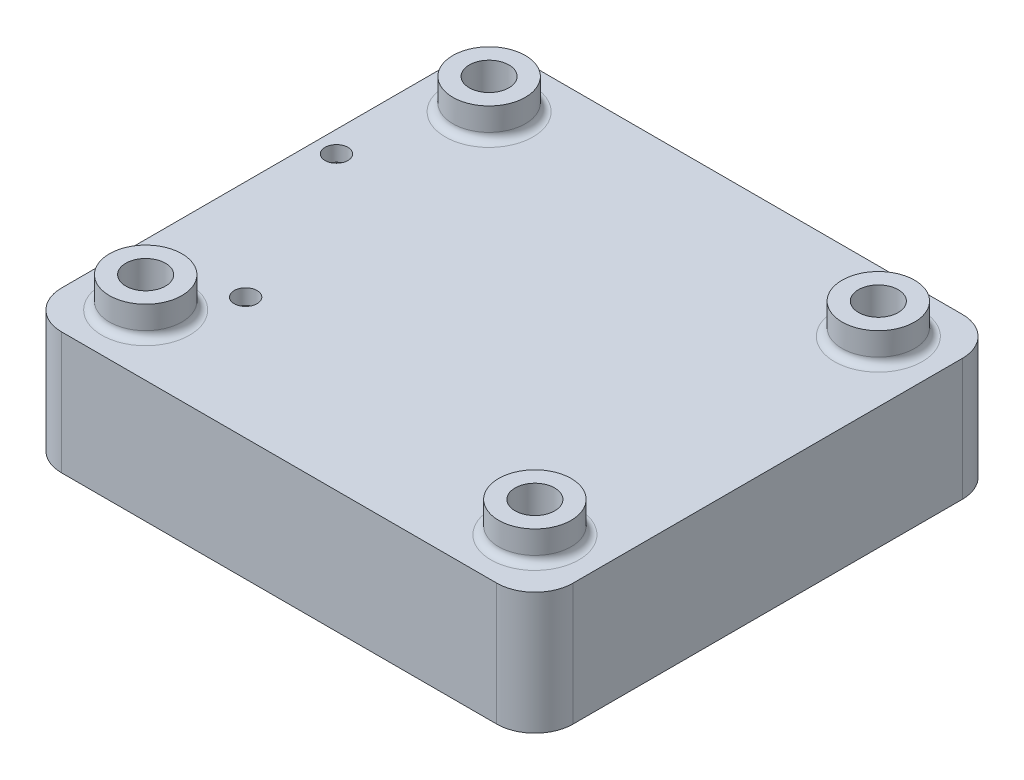
SolidWorks part; units mm, degrees
ref_plane "Plan de face" through (0, 0, 0) normal (0, 0, 1) x (1, 0, 0)
ref_plane "Plan de dessus" through (0, 0, 0) normal (0, 1, 0) x (1, 0, 0)
ref_plane "Plan de droite" through (0, 0, 0) normal (1, 0, 0) x (0, 0, -1)
sketch "Esquisse1" plane through (0, 0, 0) normal (0, 1, 0) x (1, 0, 0)
  line L1 (0, 0) -> (67, 0)
  line L2 (0, 0) -> (0, 61)
  line L3 (0, 61) -> (67, 61)
  line L4 (67, 0) -> (67, 61)
  dimension "D1" = 67
  dimension "D2" = 61
extrude "Boss.-Extru.1" add sketch "Esquisse1" along normal blind 16
sketch "Esquisse4" plane through (0, 16, 0) normal (0, 1, 0) x (1, 0, 0)
  line L0 (0, 61) -> (0, 0) construction
  line L1 (0, 0) -> (67, 0) construction
  circle A0 centre (8, 8) radius 4.75
  circle A1 centre (8, 53) radius 4.75
  circle A2 centre (59, 8) radius 4.75
  circle A3 centre (59, 53) radius 4.75
  dimension "D1" = 9.5
  dimension "D2" = 9.5
  dimension "D3" = 9.5
  dimension "D4" = 9.5
  dimension "D5" = 45
  dimension "D6" = 51
  dimension "D7" = 51
  dimension "D8" = 45
  dimension "D9" = 8
  dimension "D10" = 8
  dimension "D11" = 8
  dimension "D12" = 8
extrude "Boss.-Extru.3" add sketch "Esquisse4" along normal blind 4
sketch "Esquisse6" plane through (0, 20, 0) normal (0, 1, 0) x (1, 0, 0)
  circle A0 centre (8, 8) radius 2.6
  circle A1 centre (8, 53) radius 2.6
  circle A2 centre (59, 53) radius 2.6
  circle A3 centre (59, 8) radius 2.6
  circle A4 centre (59, 8) radius 4.75 construction
  circle A5 centre (59, 53) radius 4.75 construction
  circle A6 centre (8, 53) radius 4.75 construction
  dimension "D1" = 5.2
  dimension "D2" = 5.2
  dimension "D3" = 5.2
  dimension "D4" = 5.2
extrude "Enlèv. mat.-Extru.2" cut sketch "Esquisse6" against normal through all
fillet "Congé2" radius 1 4 edges at (59, 16, -57.75) (8, 16, -57.75) (8, 16, -12.75) (59, 16, -12.75)
fillet "Congé3" radius 5 4 edges at (0, 8, -61) (0, 8, 0) (67, 8, 0) (67, 8, -61)
sketch "Esquisse7" plane through (0, 0, 0) normal (0, -1, 0) x (1, 0, 0)
  line L0 (0, -56) -> (0, -5) construction
  line L1 (0, -41) -> (22, -41)
  line L2 (0, -41) -> (0, -13)
  line L3 (0, -13) -> (22, -13)
  line L4 (22, -41) -> (22, -13)
  line L5 (62, -61) -> (5, -61) construction
  line L7 (6.5, -41) -> (14.5, -41)
  line L8 (6.5, -41) -> (6.5, -47)
  line L9 (6.5, -47) -> (14.5, -47)
  line L10 (14.5, -41) -> (14.5, -47)
  line L11 (22, -41) -> (14.5, -41)
  line L12 (22, -41) -> (22, -61)
  line L13 (22, -61) -> (14.5, -61)
  line L14 (14.5, -41) -> (14.5, -61)
  point P12 (6.5, -44)
  line M9 (0, -5) -> (0, -56)
  line M11 (5, -61) -> (62, -61)
  dimension "D1" = 22
  dimension "D2" = 28
  dimension "D3" = 20
  dimension "D4" = 8
  dimension "D5" = 6.5
  dimension "D6" = 6
extrude "Enlèv. mat.-Extru.3" cut sketch "Esquisse7" against normal blind 14 contours L1 L4 L3 M9 | L10 L14 L12 L1 M11 | L10 L1 L8 L9 region at (11, 0, -27) region at (10.5, 0, -44) region at (18.25, 0, -51)
sketch "Esquisse8" plane through (0, 14, 0) normal (0, -1, 0) x (-1, 0, 0)
  line L0 (0, 13) -> (0, 41) construction
  line L1 (0, 13) -> (-22, 13) construction
  circle A0 centre (-2.8, 38.2) radius 1.5
  circle A1 centre (-13.1, 16) radius 1.5
  point P6 (0, 0)
  point P7 (0, 0)
  dimension "D2" = 3
  dimension "D4" = 3
  dimension "D1" = 2.8
  dimension "D3" = 10.3
  dimension "D5" = 22.2
  dimension "D6" = 3
extrude "Enlèv. mat.-Extru.4" cut sketch "Esquisse8" against normal blind 11
